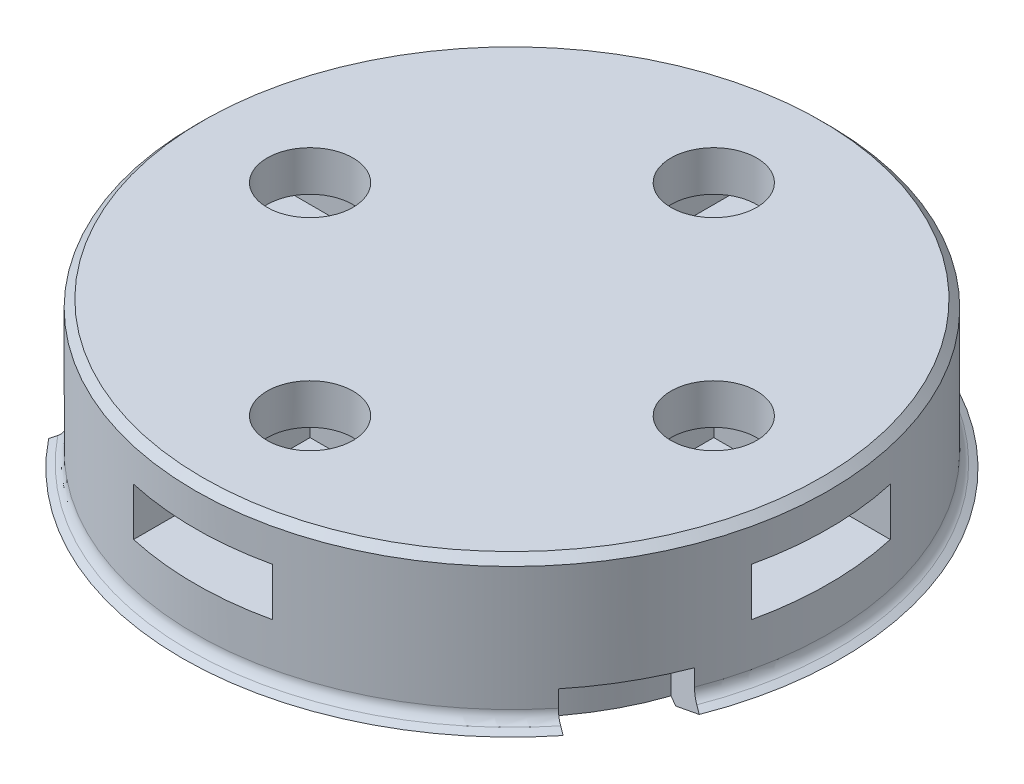
SolidWorks part; units mm, degrees
ref_plane "Front Plane" through (0, 0, 0) normal (0, 0, 1) x (1, 0, 0)
ref_plane "Top Plane" through (0, 0, 0) normal (0, 1, 0) x (1, 0, 0)
ref_plane "Right Plane" through (0, 0, 0) normal (1, 0, 0) x (0, 0, -1)
sketch "Sketch1" plane through (0, 0, 0) normal (0, 1, 0) x (1, 0, 0)
  circle A0 centre (0, 0) radius 10.05
  dimension "D1" = 20.1
extrude "Boss-Extrude1" add sketch "Sketch1" along normal blind 1.746
sketch "Sketch2" plane through (0, 1.746, 0) normal (0, 1, 0) x (1, 0, 0)
  circle A0 centre (0, 0) radius 12.55
  dimension "D1" = 25.1
extrude "Boss-Extrude2" add sketch "Sketch2" along normal blind 4
sketch "Sketch3" plane through (0, 0, 0) normal (0, -1, 0) x (1, 0, 0)
  circle A0 centre (0, 0) radius 4.5
  dimension "D1" = 9
extrude "Cut-Extrude1" cut sketch "Sketch3" against normal through all
sketch "Sketch4" plane through (0, 0, 0) normal (0, -1, 0) x (1, 0, 0)
  line L0 (0, 0) -> (0, 12.55) construction
  line L1 (0, 0) -> (0, 6.75) construction
  line L2 (0, 0) -> (5.8457, -3.375) construction
  circle A0 centre (0, 0) radius 12.55 construction
  circle A1 centre (0, 6.75) radius 2.525
  circle A2 centre (5.8457, -3.375) radius 2.525
  circle A3 centre (-5.8457, -3.375) radius 2.525
  dimension "D1" = 5.05
  dimension "D2" = 6.75
  dimension "D4" = 120
  dimension "D3" = 3
extrude "Cut-Extrude2" cut sketch "Sketch4" against normal blind 2.5
sketch "Sketch5" plane through (0, 2.5, 0) normal (0, -1, 0) x (1, 0, 0)
  circle A0 centre (0, 6.75) radius 1.75
  circle A1 centre (-5.8457, -3.375) radius 1.75
  circle A2 centre (5.8457, -3.375) radius 1.75
  dimension "D1" = 3.5
extrude "Cut-Extrude3" cut sketch "Sketch5" against normal blind 0.3
chamfer "Chamfer1" distance 0.3 angle 45 3 edges at (8.0324, 0, -4.6375) (-8.0324, 0, -4.6375) (0, 0, 9.275)
sketch "Sketch6" plane through (0, 0, 0) normal (0, -1, 0) x (1, 0, 0)
  line L0 (0, 0) -> (6.7117, 3.875) construction
  line L1 (0, 6.75) -> (5.8457, -3.375) construction
  line L2 (0, 0) -> (6.7117, 3.875) construction
  line L3 (0, 0) -> (0, -7.75) construction
  circle A0 centre (0, 0) radius 7.75 construction
  circle A1 centre (6.7117, 3.875) radius 1.1
  circle A2 centre (0, -7.75) radius 1.1
  circle A3 centre (-6.7117, 3.875) radius 1.1
  dimension "D1" = 15.5
  dimension "D2" = 2.2
  dimension "D3" = 3
  dimension "D4" = 120
extrude "Cut-Extrude4" cut sketch "Sketch6" against normal blind 2.5
ref_plane "Plane1" through (0, 1, 0) normal (0, -1, 0) x (-1, 0, 0)
ref_axis "Axis1" through (0, 5.746, 0) along (0, -1, 0)
sketch "Sketch10" plane through (0, 0, 0) normal (0, 0, 1) x (1, 0, 0)
  line L0 (10.05, 1.746) -> (13.5742, 1.746) construction
  line L2 (10.05, 0) -> (10.05, 1.746)
  line L3 (12.55, 1.746) -> (12.55, 5.746) construction
  line L4 (10.05, 1.746) -> (12.55, 1.746)
  line L11 (-10.05, 0) -> (10.05, 0) construction
  line L12 (10.05, 0) -> (10.55, 0) construction
  line L13 (10.55, 0) -> (13.5742, 1.746) construction
  line L14 (10.05, 0) -> (10.55, 0)
  line L15 (12.55, 1.746) -> (13.0621, 1.4504)
  line L17 (13.0621, 1.4504) -> (10.55, 0)
  dimension "D1" = 150
  dimension "D2" = 30
  dimension "D3" = 0.5
  dimension "D4" = 0.5121
revolve "Revolve1" add sketch "Sketch10" angle 360 about axis through (0, 5.746, 0) along (0, -1, 0)
sketch "Sketch7" plane through (0, 1, 0) normal (0, -1, 0) x (-1, 0, 0)
  line L0 (-1.975, 8.8903) -> (-1.975, 18.8903)
  line L1 (0, 10.0305) -> (-1.975, 8.8903) construction
  line L2 (-1.975, 8.8903) -> (-1.975, 6.6097)
  line L3 (-1.975, 6.6097) -> (0, 5.4695)
  line L4 (0, 5.4695) -> (1.975, 6.6097)
  line L5 (1.975, 6.6097) -> (1.975, 8.8903)
  line L6 (1.975, 8.8903) -> (0, 10.0305) construction
  line L7 (-1.975, 18.8903) -> (1.975, 18.8903)
  line L8 (1.975, 18.8903) -> (1.975, 8.8903)
  circle A0 centre (0, 7.75) radius 1.975 construction
  dimension "D1" = 3.95
  dimension "D2" = 10
extrude "Cut-Extrude5" cut sketch "Sketch7" against normal blind 1.7
sketch "Sketch11" plane through (0, 0, 0) normal (0, -1, 0) x (1, 0, 0)
  line L0 (1.975, -12.3936) -> (1.975, -6.6097) construction
  line L1 (-1.975, -19.854) -> (-1.975, -9.854)
  line L2 (1.975, -19.854) -> (1.975, -9.854)
  line L3 (-1.975, -6.6097) -> (-1.975, -12.3936) construction
  arc A0 (-1.975, -19.854) -> (1.975, -19.854) centre (0, 0) ccw
  arc A3 (-1.975, -9.854) -> (1.975, -9.854) centre (0, 0) ccw
  dimension "D1" = 10.05
  dimension "D2" = 10
extrude "Cut-Extrude6" cut sketch "Sketch11" against normal up to surface (2.7 mm away) up to face at (0, 2.7, -8.7265)
pattern_circular "CirPattern1" count 3 over 360 about axis through (0, 5.746, 0) along (0, -1, 0) of "Cut-Extrude5", "Cut-Extrude6"
fillet "Fillet1" radius 0.5 3 edges at (-10.8686, 1.746, -6.275) (0, 1.746, 12.55) (10.8686, 1.746, -6.275)
sketch "Sketch12" plane through (0, 5.746, 0) normal (0, 1, 0) x (1, 0, 0)
  circle A0 centre (0, 0) radius 12.55
  circle A1 centre (0, 0) radius 12.55 construction
extrude "Boss-Extrude3" add sketch "Sketch12" along normal blind 1.5
sketch "Sketch13" plane through (0, 7.246, 0) normal (0, 1, 0) x (1, 0, 0)
  circle A0 centre (0, 0) radius 8 construction
  circle A1 centre (0, -8) radius 1.7
  circle A2 centre (-8, 0) radius 1.7
  circle A3 centre (0, 8) radius 1.7
  circle A4 centre (8, 0) radius 1.7
  point P14 (0, 0)
  dimension "D1" = 16
  dimension "D2" = 3.4
  dimension "D3" = 4
extrude "Cut-Extrude7" cut sketch "Sketch13" against normal blind 3.5
sketch "Sketch14" [suppressed] plane through (0, 3.746, 0) normal (0, 1, 0) x (1, 0, 0)
  line L0 (-2.7, -9.5588) -> (-2.7, -14.5588)
  line L1 (0, -11.1177) -> (2.7, -9.5588) construction
  line L2 (2.7, -9.5588) -> (2.7, -6.4412)
  line L3 (2.7, -6.4412) -> (0, -4.8823)
  line L4 (0, -4.8823) -> (-2.7, -6.4412)
  line L5 (-2.7, -6.4412) -> (-2.7, -9.5588)
  line L6 (-2.7, -9.5588) -> (0, -11.1177) construction
  line L7 (-2.7, -14.5588) -> (2.7, -14.5588)
  line L8 (2.7, -14.5588) -> (2.7, -9.5588)
  circle A0 centre (0, -8) radius 2.7 construction
  dimension "D1" = 5.4
  dimension "D2" = 5
extrude "Cut-Extrude8" [suppressed] cut sketch "Sketch14" along normal blind 2.7
pattern_circular "CirPattern3" [suppressed] count 3 over 360 about axis through (0, 5.746, 0) along (0, -1, 0) of bodies 113
fillet "4 Holes Fillet" [suppressed] radius 0.5
fillet "3 Holes Fillet" [suppressed] radius 0.5
sketch "Sketch15" plane through (0, 3.746, 0) normal (0, 1, 0) x (1, 0, 0)
  line L0 (-2.75, -10.75) -> (-2.75, -15.75)
  line L1 (-2.75, -10.75) -> (2.75, -10.75) construction
  line L2 (-2.75, -10.75) -> (-2.75, -5.25)
  line L3 (-2.75, -5.25) -> (2.75, -5.25)
  line L4 (2.75, -10.75) -> (2.75, -5.25)
  line L5 (-2.75, -10.75) -> (2.75, -5.25) construction
  line L6 (-2.75, -5.25) -> (2.75, -10.75) construction
  line L7 (-2.75, -15.75) -> (2.75, -15.75)
  line L8 (2.75, -15.75) -> (2.75, -10.75)
  line L9 (-15.75, -2.75) -> (-10.75, -2.75)
  line L10 (-10.75, -2.75) -> (-5.25, -2.75)
  line L11 (-5.25, 2.75) -> (-5.25, -2.75)
  line L12 (-10.75, 2.75) -> (-5.25, 2.75)
  line L13 (-10.75, 2.75) -> (-15.75, 2.75)
  line L14 (-15.75, 2.75) -> (-15.75, -2.75)
  line L15 (-2.75, 15.75) -> (-2.75, 10.75)
  line L16 (-2.75, 10.75) -> (-2.75, 5.25)
  line L17 (2.75, 5.25) -> (-2.75, 5.25)
  line L18 (2.75, 10.75) -> (2.75, 5.25)
  line L19 (2.75, 10.75) -> (2.75, 15.75)
  line L20 (2.75, 15.75) -> (-2.75, 15.75)
  line L21 (15.75, 2.75) -> (10.75, 2.75)
  line L22 (10.75, 2.75) -> (5.25, 2.75)
  line L23 (5.25, -2.75) -> (5.25, 2.75)
  line L24 (10.75, -2.75) -> (5.25, -2.75)
  line L25 (10.75, -2.75) -> (15.75, -2.75)
  line L26 (15.75, -2.75) -> (15.75, 2.75)
  point P0 (0, -8)
  point P22 (0, 0)
  dimension "D1" = 5
  dimension "D2" = 5.5
  dimension "D3" = 4
extrude "Cut-Extrude9" cut sketch "Sketch15" along normal blind 1.9
chamfer "Chamfer2" distance 0.3 angle 45 1 edges at (0, 7.246, 12.55)
fillet "Fillet2" [suppressed] radius 0.5
fillet "Fillet3" [suppressed] radius 0.5
sketch "Sketch16" plane through (0, 0, 0) normal (0, -1, 0) x (1, 0, 0)
  circle A0 centre (0, 6.75) radius 5.25
  circle A1 centre (-5.8457, -3.375) radius 5.25
  circle A2 centre (5.8457, -3.375) radius 5.25
  dimension "D1" = 10.5
extrude "Cut-Extrude10" cut sketch "Sketch16" against normal blind 0.5
sketch "Sketch17" plane through (0, 0.5, 0) normal (0, -1, 0) x (1, 0, 0)
  line L0 (-3.496, 2.8333) -> (-2.4602, 7.3182)
  line L1 (0, 0) -> (0, 6.75) construction
  line L2 (3.496, 2.8333) -> (2.4602, 7.3182)
  line L3 (-3.496, 2.8333) -> (3.496, 2.8333)
  line L4 (4.2018, 1.611) -> (0.7057, -4.4443)
  line L5 (0.7057, -4.4443) -> (5.1076, -5.7897)
  line L6 (4.2018, 1.611) -> (7.5679, -1.5285)
  line L7 (-0.7057, -4.4443) -> (-4.2018, 1.611)
  line L8 (-4.2018, 1.611) -> (-7.5679, -1.5285)
  line L9 (-0.7057, -4.4443) -> (-5.1076, -5.7897)
  circle A0 centre (0, 6.75) radius 2.525 construction
  circle A1 centre (0, 6.75) radius 2.525 construction
  arc A2 (-2.4602, 7.3182) -> (2.4602, 7.3182) centre (0, 6.75) cw
  arc A3 (7.5679, -1.5285) -> (5.1076, -5.7897) centre (5.8457, -3.375) cw
  arc A4 (-5.1076, -5.7897) -> (-7.5679, -1.5285) centre (-5.8457, -3.375) cw
  point P14 (0, 0)
  point P15 (0, 0)
  point P26 (0, 0)
  dimension "D1" = 3
